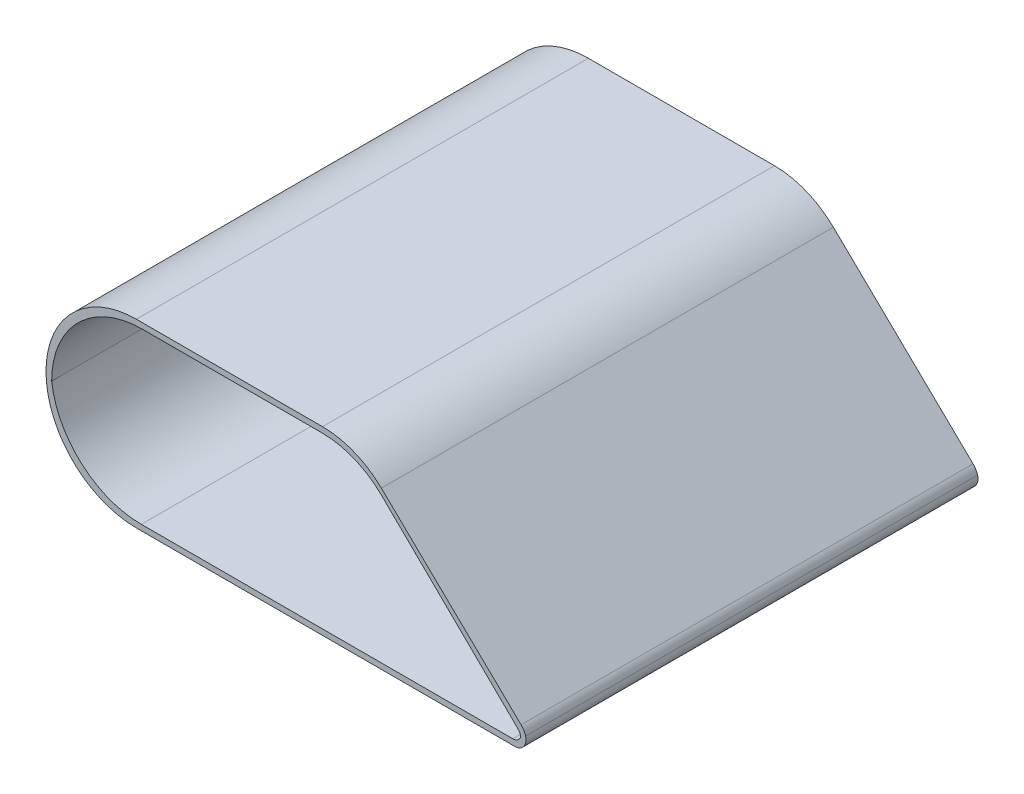
SolidWorks part; units mm, degrees
ref_plane "Front Plane" through (0, 0, 0) normal (0, 0, 1) x (1, 0, 0)
ref_plane "Top Plane" through (0, 0, 0) normal (0, 1, 0) x (1, 0, 0)
ref_plane "Right Plane" through (0, 0, 0) normal (1, 0, 0) x (0, 0, -1)
sketch "Sketch1" plane through (0, 0, 0) normal (0, 0, 1) x (1, 0, 0)
  line L1 (0, 0) -> (85, 0)
  line L2 (0, 0) -> (0, 32)
  line L3 (0, 32) -> (85, 32)
  line L4 (85, 0) -> (85, 32)
  dimension "D1" = 85
  dimension "D2" = 32
extrude "Boss-Extrude1" add sketch "Sketch1" along normal blind 80
sketch "Sketch3" plane through (0, 0, 80) normal (0, 0, 1) x (1, 0, 0)
  line L1 (85, 0) -> (85, 32) construction
  line L2 (85, 3) -> (55, 32)
  line L3 (85, 32) -> (0, 32) construction
  point P0 (80, 2.0701)
  dimension "D1" = 30
  dimension "D2" = 3
extrude "Cut-Extrude7" cut sketch "Sketch3" against normal blind 80 and the other way through all flip side to cut
sketch "Sketch6" plane through (0, 0, 80) normal (0, 0, 1) x (1, 0, 0)
  line L0 (1, 31) -> (1, 1)
  line L1 (1, 1) -> (84, 1)
  line L2 (84, 1) -> (84, 2.5351)
  line L3 (84, 2.5351) -> (55, 31)
  line L4 (55, 31) -> (1, 31)
  line L5 (55, 32) -> (0, 32) construction
  line L6 (0, 32) -> (0, 0) construction
  line L7 (0, 0) -> (85, 0) construction
  line L8 (85, 0) -> (85, 3) construction
  point P13 (55.1038, 29)
  dimension "D1" = 1
  dimension "D2" = 1
  dimension "D3" = 1
  dimension "D4" = 1
extrude "Cut-Extrude8" cut sketch "Sketch6" against normal blind 79
fillet "Fillet11" radius 16 1 edges at (1, 31, 40.5)
fillet "Fillet12" radius 16 1 edges at (1, 1, 40.5)
fillet "Fillet13" radius 16 1 edges at (0, 32, 40)
fillet "Fillet14" radius 16 1 edges at (0, 0, 40)
fillet "Fillet15" radius 15 1 edges at (55, 31, 40.5)
fillet "Fillet16" radius 15 1 edges at (55, 32, 40)
fillet "Fillet17" radius 1.5 1 edges at (84, 2.5351, 40.5)
fillet "Fillet18" radius 1.5 1 edges at (84, 1, 40.5)
fillet "Fillet21" radius 3 1 edges at (85, 3, 40)
fillet "Fillet22" radius 2 1 edges at (85, 0, 40)
sketch "Sketch16" plane through (0, 0, 0) normal (0, 0, -1) x (-1, 0, 0)
  line L0 (-16, 0) -> (-82.9621, 0) construction
  line L1 (-31.8864, 6) -> (-21.8864, 6)
  line L2 (-31.8864, 6) -> (-31.8864, 1)
  line L3 (-31.8864, 1) -> (-21.8864, 1)
  line L4 (-21.8864, 6) -> (-21.8864, 1)
  dimension "D1" = 10
  dimension "D2" = 5
  dimension "D3" = 53
  dimension "D4" = 1
sketch "Sketch17" plane through (0, 0, 0) normal (0, 0, -1) x (-1, 0, 0)
  line L0 (-16, 0) -> (-82.9621, 0) construction
  line L1 (-38.3864, 12.5) -> (-28.3864, 12.5)
  line L2 (-38.3864, 12.5) -> (-38.3864, 7.5)
  line L3 (-38.3864, 7.5) -> (-28.3864, 7.5)
  line L4 (-28.3864, 12.5) -> (-28.3864, 7.5)
  dimension "D1" = 10
  dimension "D2" = 5
  dimension "D3" = 46.5
  dimension "D4" = 7.5
sketch "Sketch18" plane through (0, 0, 0) normal (0, 0, -1) x (-1, 0, 0)
  line L0 (-16, 0) -> (-82.9621, 0) construction
  line L1 (-31.8864, 17.5) -> (-46.8864, 17.5)
  line L2 (-31.8864, 17.5) -> (-31.8864, 22.5)
  line L3 (-31.8864, 22.5) -> (-46.8864, 22.5)
  line L4 (-46.8864, 17.5) -> (-46.8864, 22.5)
  dimension "D1" = 15
  dimension "D2" = 5
  dimension "D3" = 17.5
  dimension "D4" = 38
extrude "Cut-Extrude14" cut sketch "Sketch18" against normal blind 79
extrude "Cut-Extrude15" cut sketch "Sketch17" against normal blind 79
extrude "Cut-Extrude16" cut sketch "Sketch16" against normal blind 79
fillet "Fillet29" radius 2.5 1 edges at (31.8864, 22.5, 0.5)
fillet "Fillet30" radius 2.5 1 edges at (31.8864, 17.5, 0.5)
fillet "Fillet31" radius 2.5 1 edges at (46.8864, 22.5, 0.5)
fillet "Fillet32" radius 2.5 1 edges at (28.3864, 12.5, 0.5)
fillet "Fillet33" radius 2.5 1 edges at (28.3864, 7.5, 0.5)
fillet "Fillet34" radius 2.5 1 edges at (38.3864, 12.5, 0.5)
fillet "Fillet35" radius 2.5 1 edges at (21.8864, 6, 0.5)
fillet "Fillet36" radius 2.5 1 edges at (21.8864, 1, 0.5)
fillet "Fillet37" radius 2.5 1 edges at (31.8864, 6, 0.5)
